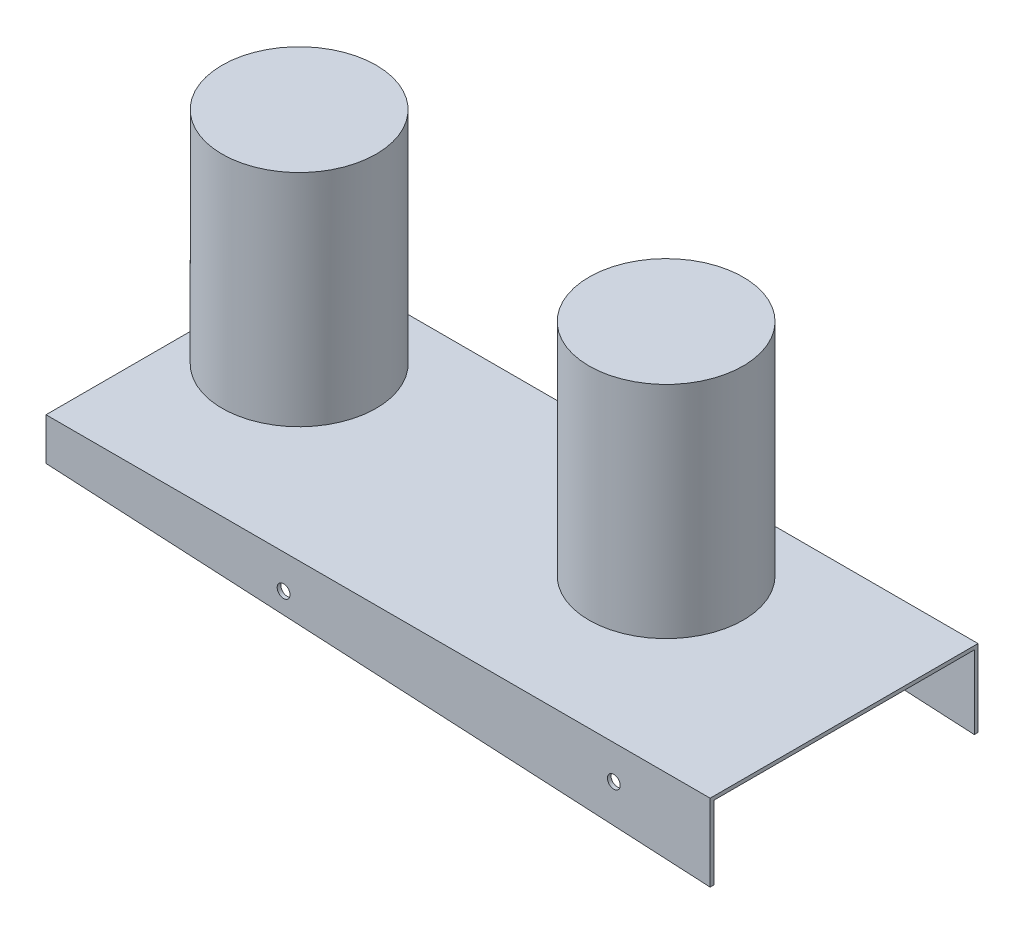
SolidWorks part; units mm, degrees
ref_plane "Front Plane" through (0, 0, 0) normal (0, 0, 1) x (1, 0, 0)
ref_plane "Top Plane" through (0, 0, 0) normal (0, 1, 0) x (1, 0, 0)
ref_plane "Right Plane" through (0, 0, 0) normal (1, 0, 0) x (0, 0, -1)
sketch "Sketch1" plane through (0, 0, 0) normal (0, 1, 0) x (1, 0, 0)
  line L1 (-181, -73) -> (181, -73)
  line L2 (-181, -73) -> (-181, 73)
  line L3 (-181, 73) -> (181, 73)
  line L4 (181, -73) -> (181, 73)
  line L5 (-181, -73) -> (181, 73) construction
  line L6 (-181, 73) -> (181, -73) construction
  point P0 (0, 0)
  dimension "D1" = 362
  dimension "D2" = 146
extrude "Boss-Extrude1" add sketch "Sketch1" against normal blind 2
sketch "Sketch2" plane through (0, 0, 0) normal (0, 1, 0) x (1, 0, 0)
  line L0 (181, -73) -> (181, 73) construction
  line L1 (-181, 73) -> (181, 73)
  line L2 (-181, 73) -> (-181, 71)
  line L3 (-181, 71) -> (181, 71)
  line L4 (181, 73) -> (181, 71)
  line L5 (0, 0) -> (181, 0) construction
  line L6 (-181, -71) -> (181, -71)
  line L7 (181, -73) -> (181, -71)
  line L8 (-181, -73) -> (181, -73)
  line L9 (-181, -73) -> (-181, -71)
  dimension "D1" = 2
extrude "Boss-Extrude2" add sketch "Sketch2" against normal blind 42
sketch "Sketch3" plane through (0, 0, 0) normal (0, 0, 1) x (1, 0, 0)
  line L0 (-181, -42) -> (181, -42) construction
  line L1 (-181, -42) -> (181, -42)
  line L2 (-181, 0) -> (181, 0) construction
  line L3 (-181, 0) -> (181, 0)
  line L4 (-181, 0) -> (-181, -23) construction
  line L5 (-181, -42) -> (-181, 0) construction
  line L6 (-181, -23) -> (181, -42)
  line L7 (-181, -23) -> (-181, -42)
  line L8 (181, -42) -> (-181, -42)
  dimension "D1" = 23
extrude "Cut-Extrude1" cut sketch "Sketch3" against normal through all both and the other way through all contours L6 L7 L1 region at (-60.3333, -35.6667, 0)
sketch "Sketch4" plane through (0, 0, 0) normal (0, 0, 1) x (1, 0, 0)
  line L0 (181, 0) -> (132, 0) construction
  line L1 (-181, 0) -> (181, 0) construction
  line L2 (132, 0) -> (132, -15) construction
  line L3 (132, -15) -> (128.5, -15) construction
  line L4 (128.5, -15) -> (128.5, -18.5) construction
  line L5 (128.5, -18.5) -> (-51.5, -18.5) construction
  circle A0 centre (128.5, -18.5) radius 3.5
  circle A1 centre (-51.5, -18.5) radius 3.5
  dimension "D5" = 7
  dimension "D7" = 7
  dimension "D1" = 49
  dimension "D2" = 15
  dimension "D3" = 3.5
  dimension "D4" = 3.5
  dimension "D6" = 180
extrude "Cut-Extrude2" cut sketch "Sketch4" against normal through all both and the other way through all
sketch "Sketch5" plane through (0, 0, 0) normal (0, 1, 0) x (1, 0, 0)
  line L0 (181, 20) -> (64, 20) construction
  line L1 (181, -73) -> (181, 73) construction
  line L2 (181, 73) -> (-181, 73) construction
  line L3 (64, 20) -> (-136.025, 20) construction
  circle A0 centre (64, 20) radius 42
  circle A1 centre (-136.025, 20) radius 42
  dimension "D2" = 84
  dimension "D5" = 84
  dimension "D1" = 117
  dimension "D3" = 53
  dimension "D4" = 200.025
extrude "Boss-Extrude3" add sketch "Sketch5" along normal blind 120
